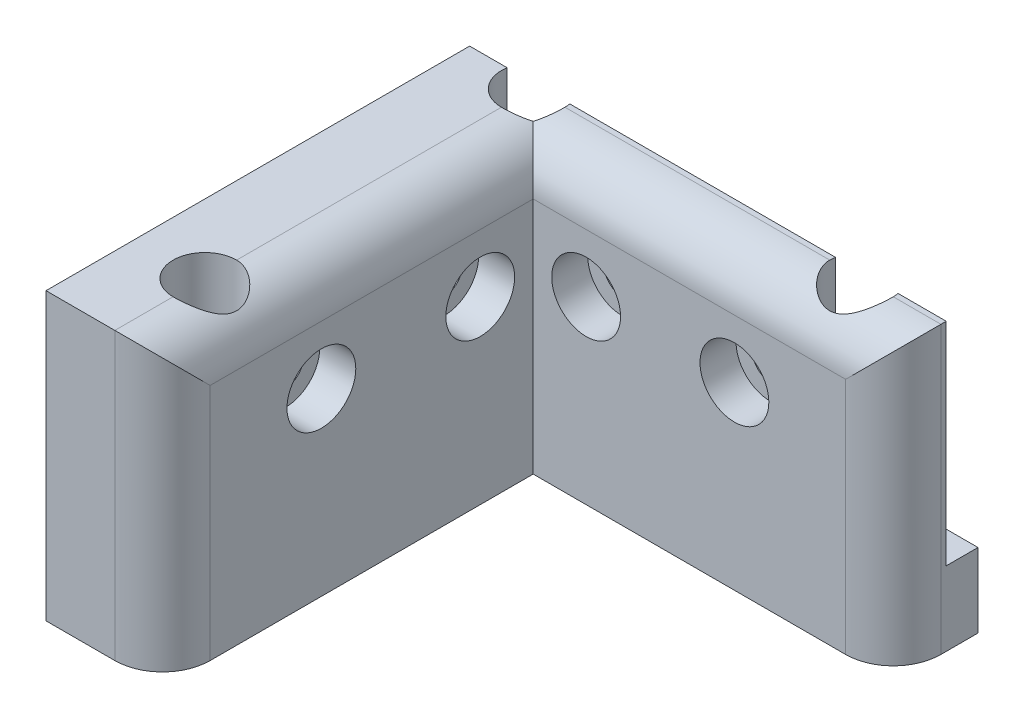
SolidWorks part; units mm, degrees
material "ABS"
ref_plane "Front Plane" through (0, 0, 0) normal (0, 0, 1) x (1, 0, 0)
ref_plane "Top Plane" through (0, 0, 0) normal (0, 1, 0) x (1, 0, 0)
ref_plane "Right Plane" through (0, 0, 0) normal (1, 0, 0) x (0, 0, -1)
sketch "Sketch1" plane through (0, 0, 0) normal (0, 1, 0) x (1, 0, 0)
  line L1 (0, 0) -> (45, 0)
  line L2 (0, 0) -> (0, 40)
  line L3 (0, 40) -> (45, 40)
  line L4 (45, 0) -> (45, 40)
  dimension "D1" = 45
  dimension "D2" = 40
extrude "Boss-Extrude1" add sketch "Sketch1" along normal blind 29
sketch "Sketch33" plane through (0, 29, 0) normal (0, 1, 0) x (1, 0, 0)
  line L0 (0, 40) -> (0, 0) construction
  line L1 (45, 0) -> (11, 0)
  line L2 (45, 0) -> (45, 35)
  line L3 (45, 35) -> (11, 35)
  line L4 (11, 0) -> (11, 35)
  line L5 (45, 40) -> (0, 40) construction
  dimension "D1" = 11
  dimension "D2" = 5
extrude "Cut-Extrude7" cut sketch "Sketch33" against normal through all
sketch "Sketch39" plane through (0, 0, -40) normal (0, 0, -1) x (-1, 0, 0)
  line L0 (0, 29) -> (0, 0) construction
  line L1 (-45, 0) -> (0, 0)
  line L2 (-45, 0) -> (-45, 9)
  line L3 (-45, 9) -> (0, 9)
  line L4 (0, 0) -> (0, 9)
  dimension "D1" = 9
extrude "Boss-Extrude2" add sketch "Sketch39" along normal blind 3
sketch "Sketch21" plane through (0, 29, 0) normal (0, 1, 0) x (1, 0, 0)
  line L0 (45, 40) -> (0, 40) construction
  circle A1 centre (6.5, 39.5) radius 1.75
  circle A2 centre (6.5, 8.5) radius 1.75
  circle A3 centre (37.5, 39.5) radius 1.75
  dimension "D3" = 0.5
  dimension "D4" = 3.5
  dimension "D7" = 3.5
  dimension "D8" = 3.5
  dimension "D1" = 0.5
  dimension "D2" = 31
extrude "Cut-Extrude6" cut sketch "Sketch21" against normal through all both and the other way through all
sketch "Sketch34" plane through (0, 29, 0) normal (0, 1, 0) x (1, 0, 0)
  circle A0 centre (6.5, 8.5) radius 3
  circle A1 centre (6.5, 39.5) radius 3
  circle A2 centre (37.5, 39.5) radius 3
  dimension "D1" = 6
  dimension "D2" = 6
  dimension "D3" = 6
extrude "Cut-Extrude8" cut sketch "Sketch34" against normal blind 23
hole_wizard "CBORE for M3 Hex Socket Head Cap Screw1" positions "Sketch35" profile "Sketch36" counterbore size "M3" standard "ISO" end condition through all
sketch "Sketch35" plane through (11, 0, 0) normal (1, 0, 0) x (0, 0, -1)
  line L1 (0, 0) -> (0, 29) construction
  line L2 (35, 0) -> (35, 29) construction
  line L3 (35, 29) -> (0, 29) construction
  point P0 (15, 19)
  point P2 (30, 19)
  dimension "D1" = 10
  dimension "D2" = 10
  dimension "D3" = 15
  dimension "D4" = 5
sketch "Sketch36" plane through (11, 19, -15) normal (0, 1, 0) x (0, 0, -1)
  line L0 (0, 0) -> (0, 11)
  line L1 (0, 11) -> (1.7, 11)
  line L3 (1.7, 11) -> (1.7, 3.4)
  line L4 (1.7, 3.4) -> (3.25, 3.4)
  line L5 (3.25, 3.4) -> (3.25, 0)
  line L7 (3.25, 0) -> (0, 0)
  line L11 (0, -6.35) -> (0, 107.95) construction
  dimension "Thru Hole Dia." = 3.4
  dimension "Thru Hole Depth" = 11
  dimension "C'Bore Dia." = 6.5
  dimension "C'Bore Depth" = 3.4
hole_wizard "CBORE for M3 Hex Socket Head Cap Screw2" positions "Sketch37" profile "Sketch38" counterbore size "M3" standard "ISO" end condition through all
sketch "Sketch37" plane through (0, 0, -35) normal (0, 0, 1) x (1, 0, 0)
  line L1 (11, 0) -> (11, 29) construction
  line L2 (45, 0) -> (45, 29) construction
  line L3 (45, 29) -> (11, 29) construction
  point P0 (16, 19)
  point P2 (30, 19)
  dimension "D1" = 10
  dimension "D2" = 10
  dimension "D3" = 5
  dimension "D4" = 15
sketch "Sketch38" plane through (16, 19, -35) normal (1, 0, 0) x (0, -1, 0)
  line L0 (0, 0) -> (0, 8)
  line L1 (0, 8) -> (1.7, 8)
  line L3 (1.7, 8) -> (1.7, 3.4)
  line L4 (1.7, 3.4) -> (3.25, 3.4)
  line L5 (3.25, 3.4) -> (3.25, 0)
  line L7 (3.25, 0) -> (0, 0)
  line L11 (0, -6.35) -> (0, 107.95) construction
  dimension "Thru Hole Dia." = 3.4
  dimension "Thru Hole Depth" = 8
  dimension "C'Bore Dia." = 6.5
  dimension "C'Bore Depth" = 3.4
fillet "Fillet1" radius 4.5 4 edges at (11, 14.5, 0) (45, 14.5, -35) (28, 29, -35) (11, 29, -17.5)
sketch "Sketch40" plane through (0, 0, 0) normal (-1, 0, 0) x (0, 0, 1)
  line L0 (-43, 0) -> (-43, 9) construction
  line L1 (-43, 2) -> (0, 2)
  line L2 (-43, 2) -> (-43, 0)
  line L3 (-43, 0) -> (0, 0)
  line L4 (0, 2) -> (0, 0)
  dimension "D1" = 2
extrude "Cut-Extrude9" cut sketch "Sketch40" against normal through all
mirror "Mirror1" [suppressed] of bodies 125 122
delete or keep bodies "Body-Delete/Keep 1" [suppressed] type delete bodies bodies 125
